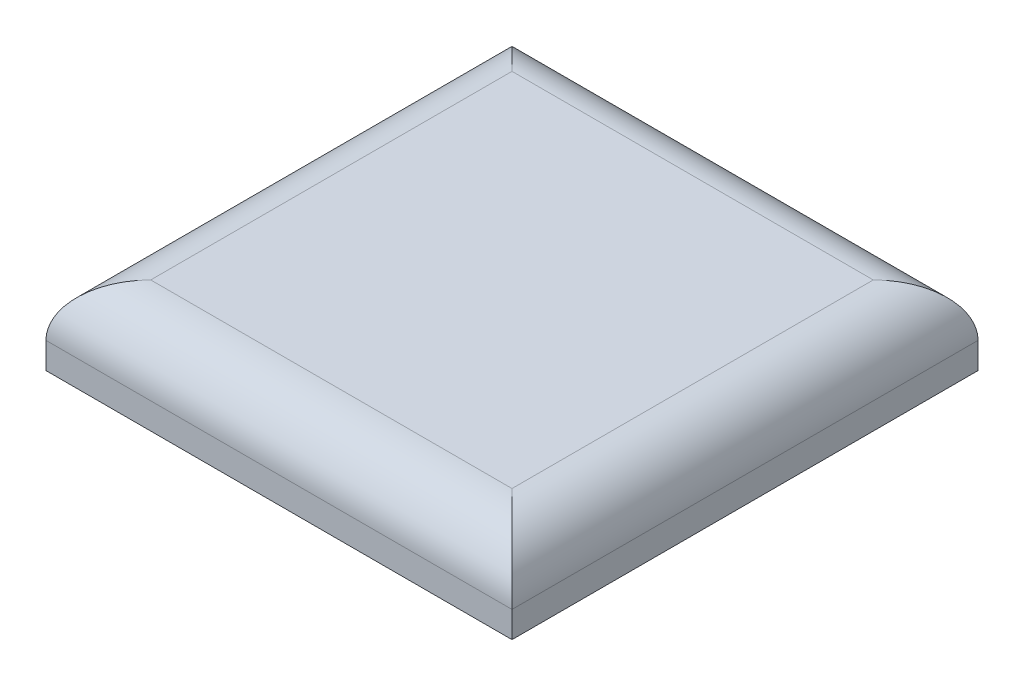
SolidWorks part; units mm, degrees
ref_plane "Спереди" through (0, 0, 0) normal (0, 0, 1) x (1, 0, 0)
ref_plane "Сверху" through (0, 0, 0) normal (0, 1, 0) x (1, 0, 0)
ref_plane "Справа" through (0, 0, 0) normal (1, 0, 0) x (0, 0, -1)
sketch "Эскиз1" plane through (0, 0, 0) normal (0, 1, 0) x (1, 0, 0)
  line L1 (-8.9, -8.9) -> (8.9, -8.9)
  line L2 (-8.9, -8.9) -> (-8.9, 8.9)
  line L3 (-8.9, 8.9) -> (8.9, 8.9)
  line L4 (8.9, -8.9) -> (8.9, 8.9)
  line L5 (-8.9, -8.9) -> (8.9, 8.9) construction
  line L6 (-8.9, 8.9) -> (8.9, -8.9) construction
  point P0 (0, 0)
extrude "Бобышка-Вытянуть1" add sketch "Эскиз1" along normal blind 3
fillet "Скругление1" radius 2 4 edges at (8.9, 3, 0) (0, 3, -8.9) (-8.9, 3, 0) (0, 3, 8.9) type face fillet first side face at (0, 3, 0) second side face at (0, 1.5, -8.9) second side face at (8.9, 1.5, 0) second side face at (0, 1.5, 8.9) second side face at (-8.9, 1.5, 0)
